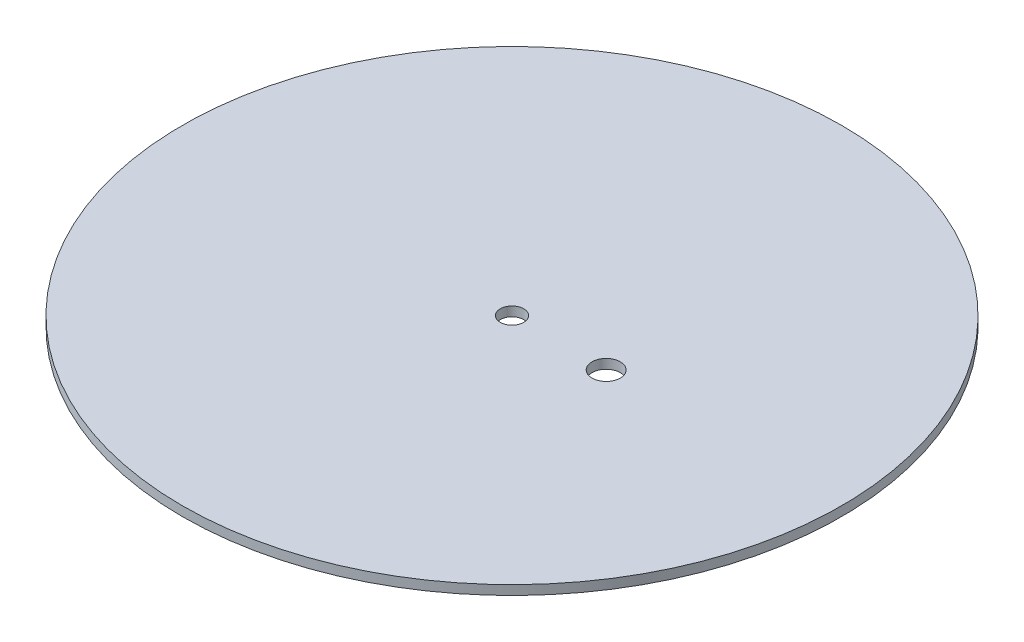
SolidWorks part; units mm, degrees
ref_plane "Front Plane" through (0, 0, 0) normal (0, 0, 1) x (1, 0, 0)
ref_plane "Top Plane" through (0, 0, 0) normal (0, 1, 0) x (1, 0, 0)
ref_plane "Right Plane" through (0, 0, 0) normal (1, 0, 0) x (0, 0, -1)
sketch "Sketch1" plane through (0, 0, 0) normal (0, 1, 0) x (1, 0, 0)
  circle A0 centre (0, 0) radius 70
  dimension "D1" = 140
extrude "Boss-Extrude1" add sketch "Sketch1" along normal blind 2
ref_axis "Axis1" through (0, 58.7719, 0) along (0, -1, 0)
sketch "Sketch3" plane through (0, 2, 0) normal (0, 1, 0) x (1, 0, 0)
  circle A0 centre (0, 0) radius 2.5
  circle A1 centre (20, 0) radius 3
  dimension "D1" = 6
  dimension "D2" = 5
  dimension "D3" = 20
extrude "Cut-Extrude1" cut sketch "Sketch3" against normal through all
